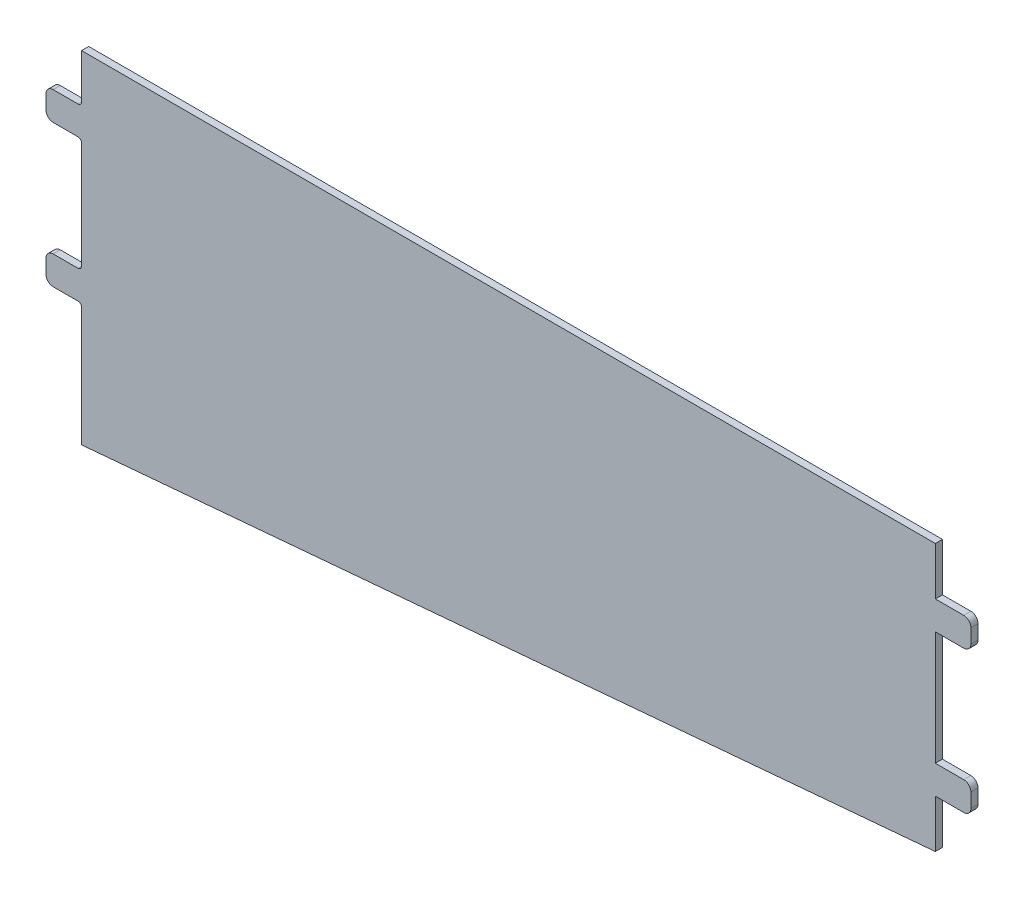
SolidWorks part; units mm, degrees
ref_plane "Front Plane" through (0, 0, 0) normal (0, 0, 1) x (1, 0, 0)
ref_plane "Top Plane" through (0, 0, 0) normal (0, 1, 0) x (1, 0, 0)
ref_plane "Right Plane" through (0, 0, 0) normal (1, 0, 0) x (0, 0, -1)
sketch "Sketch1" plane through (0, 0, 0) normal (0, 0, 1) x (1, 0, 0)
  line L1 (190.5, 76.2) -> (-190.5, 76.2)
  line L2 (190.5, 76.2) -> (190.5, -76.2)
  line L3 (190.5, -76.2) -> (-190.5, -76.2)
  line L4 (-190.5, 76.2) -> (-190.5, -76.2)
  line L5 (190.5, 76.2) -> (-190.5, -76.2) construction
  line L6 (190.5, -76.2) -> (-190.5, 76.2) construction
  point P0 (0, 0)
  dimension "D1" = 381
  dimension "D2" = 152.4
extrude "Boss-Extrude1" add sketch "Sketch1" along normal mid plane 3.175
sketch "Sketch5" plane through (0, 0, 1.5875) normal (0, 0, 1) x (1, 0, 0)
  line L0 (-190.5, -76.2) -> (190.5, -42.8668)
  line L1 (190.5, -76.2) -> (190.5, 76.2) construction
  line L2 (190.5, -42.8668) -> (190.5, -76.2)
  line L3 (190.5, -76.2) -> (-190.5, -76.2)
  dimension "D1" = 5
extrude "Cut-Extrude1" cut sketch "Sketch5" against normal through all
sketch "Sketch3" plane through (0, 0, 1.5875) normal (0, 0, 1) x (1, 0, 0)
  line L0 (190.5, -42.8668) -> (190.5, 76.2) construction
  line L2 (-190.5, -8.7334) -> (-190.5, -21.4334)
  line L3 (-190.5, -8.7334) -> (-206.375, -8.7334)
  line L4 (-206.375, -8.7334) -> (-206.375, -21.4334)
  line L5 (-206.375, -21.4334) -> (-190.5, -21.4334)
  line L6 (190.5, 16.6666) -> (227.3092, 16.6666) construction
  line L7 (-206.375, 54.7666) -> (-190.5, 54.7666)
  line L8 (-206.375, 42.0666) -> (-206.375, 54.7666)
  line L9 (-190.5, 42.0666) -> (-206.375, 42.0666)
  line L10 (-190.5, 42.0666) -> (-190.5, 54.7666)
  line L11 (-190.5, 76.2) -> (-190.5, -76.2) construction
  point P0 (-198.4375, -8.7334)
  point P8 (-190.5, 0)
  dimension "D1" = 12.7
  dimension "D2" = 15.875
  dimension "D3" = 25.4
extrude "Boss-Extrude2" add sketch "Sketch3" against normal up to surface (3.175 mm away) contours L5 L2 L3 L4 | L7 L10 L9 L8 up to face at (0, 8.3333, -1.5875)
fillet "Fillet1" radius 3.175 4 edges at (-206.375, -21.4334, 0) (-206.375, -8.7334, 0) (-206.375, 54.7666, 0) (-206.375, 42.0666, 0)
mirror "Mirror1" about plane through (0, 0, 0) normal (1, 0, 0) of "Fillet1", "Boss-Extrude2"
fillet "Fillet2" radius 1.5875 4 edges at (-190.5, -21.4334, 0) (-190.5, -8.7334, 0) (-190.5, 42.0666, 0) (-190.5, 54.7666, 0)
